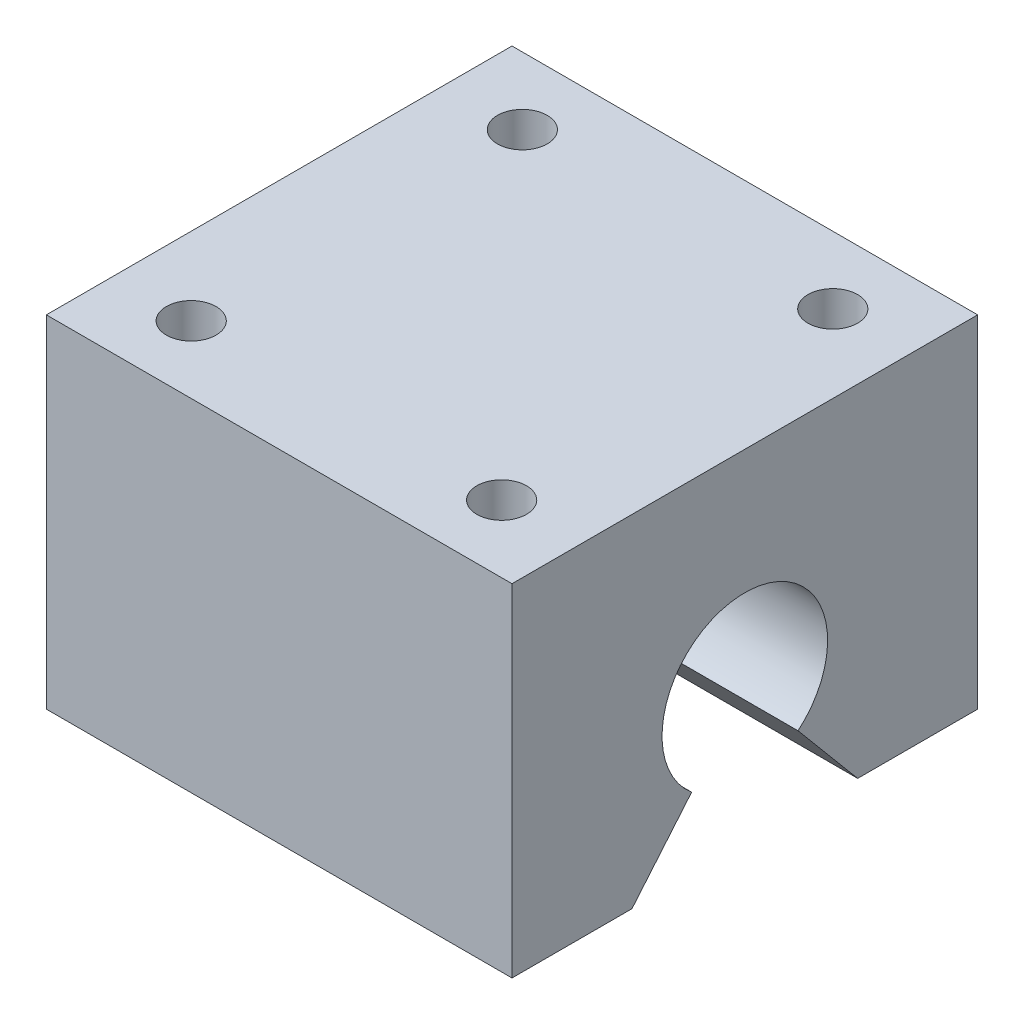
SolidWorks part; units mm, degrees
ref_plane "Спереди" through (0, 0, 0) normal (0, 0, 1) x (1, 0, 0)
ref_plane "Сверху" through (0, 0, 0) normal (0, 1, 0) x (1, 0, 0)
ref_plane "Справа" through (0, 0, 0) normal (1, 0, 0) x (0, 0, -1)
sketch "Эскиз1" plane through (0, 0, 0) normal (1, 0, 0) x (0, 0, -1)
  line L0 (0, -12.8294) -> (0, 31.9638) construction
  line L1 (-22.5, 20) -> (22.5, 20)
  line L2 (-22.5, 20) -> (-22.5, -13)
  line L3 (-22.5, -13) -> (-10.9083, -13)
  line L4 (22.5, 20) -> (22.5, -13)
  line L5 (0, 8) -> (22.5, 20) construction
  line L6 (0, 8) -> (-22.5, 20) construction
  line L7 (-5.1423, -6.1284) -> (-10.9083, -13)
  line L8 (5.1423, -6.1284) -> (10.9083, -13)
  line L9 (10.9083, -13) -> (22.5, -13)
  arc A0 (5.1423, -6.1284) -> (-5.1423, -6.1284) centre (0, 0) ccw
  dimension "D1" = 16
  dimension "D2" = 45
  dimension "D3" = 33
  dimension "D4" = 20
  dimension "D5" = 40
  dimension "D6" = 40
extrude "Бобышка-Вытянуть1" add sketch "Эскиз1" along normal blind 45
sketch "Эскиз2" plane through (0, 20, 0) normal (0, 1, 0) x (1, 0, 0)
  line L0 (22.5, 22.5) -> (22.5, -22.5) construction
  line L1 (45, 22.5) -> (0, 22.5) construction
  line L2 (45, -22.5) -> (0, -22.5) construction
  line L4 (0, 0) -> (45, 0) construction
  line L5 (45, 22.5) -> (45, -22.5) construction
  line L6 (37.5, -16) -> (7.5, -16) construction
  line L7 (37.5, -16) -> (37.5, 16) construction
  line L8 (37.5, 16) -> (7.5, 16) construction
  line L9 (7.5, -16) -> (7.5, 16) construction
  line L10 (37.5, -16) -> (7.5, 16) construction
  line L11 (37.5, 16) -> (7.5, -16) construction
  circle A0 centre (7.5, 16) radius 2.4
  circle A1 centre (37.5, 16) radius 2.4
  circle A2 centre (37.5, -16) radius 2.4
  circle A3 centre (7.5, -16) radius 2.4
  point P6 (22.5, 0)
  dimension "D3" = 4.8
  dimension "D4" = 4.8
  dimension "D5" = 4.8
  dimension "D6" = 4.8
  dimension "D1" = 30
  dimension "D2" = 32
extrude "Вырез-Вытянуть1" cut sketch "Эскиз2" against normal blind 9
ref_axis "Ось1" through (55.1878, 0, 0) along (-1, 0, 0)
ref_axis "Ось2" through (37.5, 11, -16) along (0, 1, 0)
ref_axis "Ось3" through (7.5, 11, 16) along (0, 1, 0)
ref_axis "Ось5" through (7.5, 11, -16) along (0, 1, 0)
ref_axis "Ось6" through (37.5, 11, 16) along (0, 1, 0)
